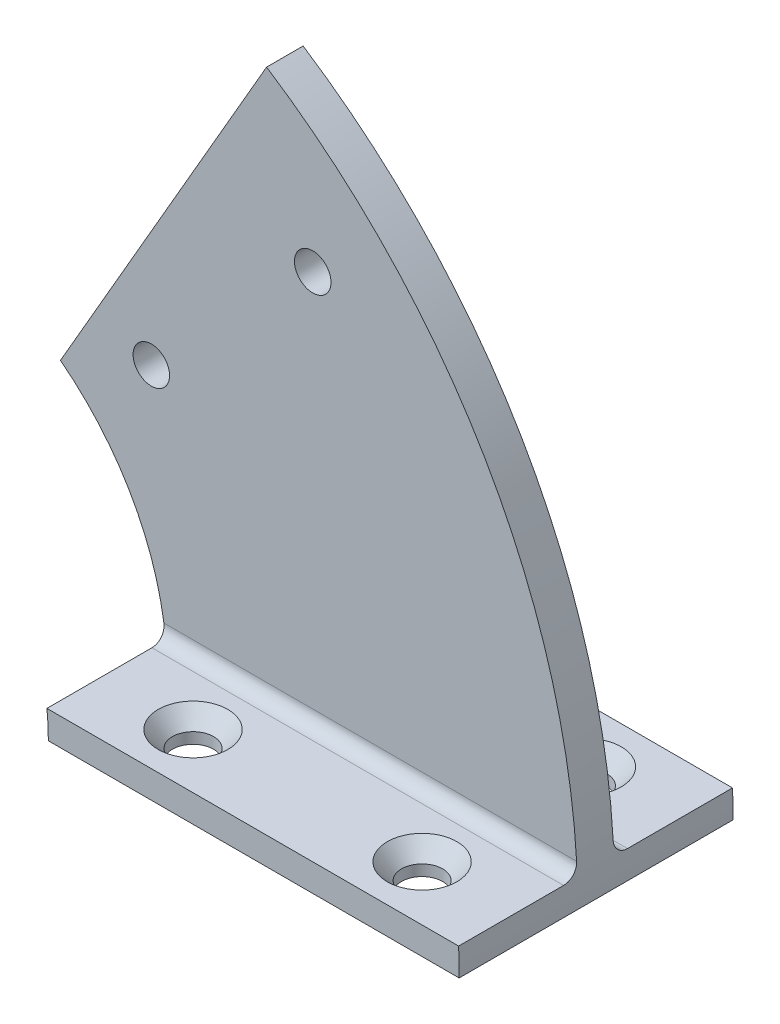
SolidWorks part; units mm, degrees
ref_plane "Front Plane" through (0, 0, 0) normal (0, 0, 1) x (1, 0, 0)
ref_plane "Top Plane" through (0, 0, 0) normal (0, 1, 0) x (1, 0, 0)
ref_plane "Right Plane" through (0, 0, 0) normal (1, 0, 0) x (0, 0, -1)
other "Configuration Table"
sketch "Sketch1" plane through (0, 0, 0) normal (0, 0, 1) x (1, 0, 0)
  line L0 (0, 0) -> (15, 25.9808) construction
  line L1 (37.5, 64.9519) -> (15, 25.9808) construction
  line L2 (30, 0) -> (75, 0)
  line L3 (0, 0) -> (28.2843, 28.2843) construction
  line L4 (28.2843, 28.2843) -> (45.9619, 45.9619) construction
  line L5 (40.9107, 62.8595) -> (18.3302, 23.7488)
  line L6 (40.9641, 62.9519) -> (18.4641, 23.9808) construction
  line L7 (29.8496, 3) -> (74.94, 3)
  line L8 (30, 3) -> (75, 3) construction
  arc A0 (18.3302, 23.7488) -> (30, 0) centre (0, 0) cw
  arc A1 (40.9107, 62.8595) -> (75, 0) centre (0, 0) cw
  arc A2 (65, 0) -> (32.5, 56.2917) centre (0, 0) ccw construction
  arc A3 (40, 0) -> (20, 34.641) centre (0, 0) ccw construction
  circle A4 centre (28.2843, 28.2843) radius 2
  circle A5 centre (45.9619, 45.9619) radius 2
  arc A6 (18.3302, 23.7488) -> (15, 25.9808) centre (0, 0) ccw construction
  point P19 (21.3546, 28.9872)
  point P20 (0, 0)
  dimension "D2" = 75
  dimension "D4" = 4
  dimension "D6" = 10
  dimension "D1" = 30
  dimension "D3" = 60
  dimension "D5" = 4
  dimension "D7" = 25
  dimension "D8" = 45
  dimension "D9" = 3
extrude "Boss-Extrude1" add sketch "Sketch1" along normal mid plane 4 contours A1 L5 A0 L7 A5 A4 region at (47.307, 26.5626, 0)
extrude "Boss-Extrude2" add sketch "Sketch1<3>" along normal mid plane 30 contours A1 L7 A0 L2 region at (52.4649, 1.5005, 0)
sketch "Sketch1<3>" plane through (0, 0, 0) normal (0, 0, 1) x (1, 0, 0) same geometry as "Sketch1"
sketch "Sketch2" plane through (0, 0, -2) normal (0, 0, -1) x (-1, 0, 0)
  line L0 (-40.9107, 62.8595) -> (-18.3302, 23.7488) construction
  line L1 (-47.9827, 42.4619) -> (-43.9412, 42.4619)
  line L2 (-43.9412, 42.4619) -> (-41.9205, 45.9619)
  line L3 (-41.9205, 45.9619) -> (-43.9412, 49.4619)
  line L4 (-43.9412, 49.4619) -> (-47.9827, 49.4619)
  line L5 (-47.9827, 49.4619) -> (-50.0034, 45.9619)
  line L6 (-50.0034, 45.9619) -> (-47.9827, 42.4619)
  line L7 (-30.305, 24.7843) -> (-26.2635, 24.7843)
  line L8 (-26.2635, 24.7843) -> (-24.2428, 28.2843)
  line L9 (-24.2428, 28.2843) -> (-26.2635, 31.7843)
  line L10 (-26.2635, 31.7843) -> (-30.305, 31.7843)
  line L11 (-30.305, 31.7843) -> (-32.3257, 28.2843)
  line L12 (-32.3257, 28.2843) -> (-30.305, 24.7843)
  circle A0 centre (-45.9619, 45.9619) radius 3.5 construction
  circle A1 centre (-28.2843, 28.2843) radius 3.5 construction
  circle A2 centre (-45.9619, 45.9619) radius 6
  circle A3 centre (-28.2843, 28.2843) radius 6
  dimension "D3" = 12
  dimension "D1" = 7
  dimension "D2" = 7
extrude "Boss-Extrude3" add sketch "Sketch2" along normal blind 2.5
sketch "Sketch3" plane through (0, 3, 0) normal (0, 1, 0) x (1, 0, 0)
  line L0 (29.8496, 15) -> (74.94, 15) construction
  line L1 (29.8496, 2) -> (29.8496, 15) construction
  line L2 (74.94, 2) -> (74.94, 15) construction
  line L3 (29.8496, -15) -> (74.94, -15) construction
  point P0 (64.94, -9)
  point P2 (39.8496, -9)
  point P4 (39.8496, 9)
  point P6 (64.94, 9)
  point P17 (0, 0)
  point P18 (0, 0)
  point P19 (0, 0)
  point P20 (0, 0)
  dimension "D1" = 6
  dimension "D2" = 10
  dimension "D3" = 10
  dimension "D4" = 6
hole_wizard "CSK for #8 Flat Head Socket Cap Screw1" positions "Sketch3" profile "Sketch4" countersink size "#8" standard "ANSI Inch"
sketch "Sketch4" plane through (64.94, 3, 9) normal (1, 0, 0) x (0, 0, 1)
  line L0 (0, 0) -> (0, 15.7088)
  line L1 (0, 15.7088) -> (2.2479, 15)
  line L2 (2.2479, 15) -> (2.2479, 1.797)
  line L3 (2.2479, 1.797) -> (3.81, 0)
  line L5 (3.81, 0) -> (0, 0)
  line L6 (-2.2479, 1.797) -> (-3.81, 0) construction
  line L10 (0, 15.7088) -> (-2.2479, 15) construction
  line L11 (0, -6.35) -> (0, 107.95) construction
  dimension "Hole Dia." = 4.4958
  dimension "Hole Depth" = 15
  dimension "Near C'Sink Dia." = 7.62
  dimension "Near C'Sink Angle" = 82
  dimension "Drill Angle" = 145
fillet "Fillet1" radius 1.5 4 edges at (52.3948, 3, -2) (52.3948, 3, 2) (34.2843, 28.2843, -2) (51.9619, 45.9619, -2)
